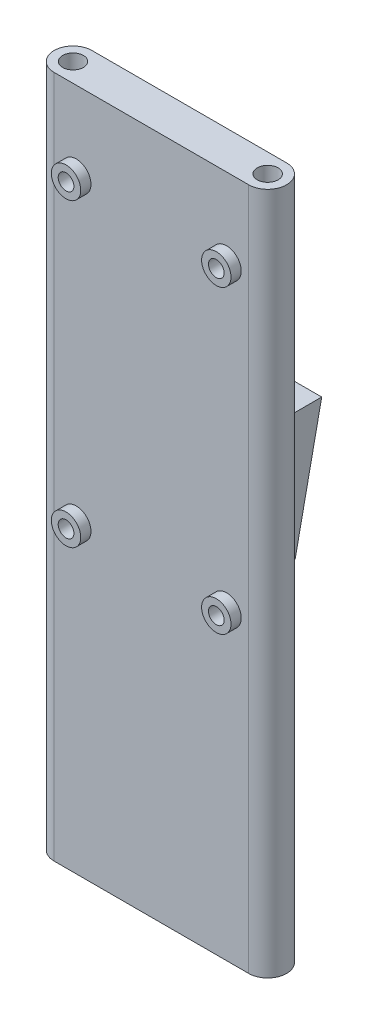
SolidWorks part; units mm, degrees
ref_plane "Front Plane" through (0, 0, 0) normal (0, 0, 1) x (1, 0, 0)
ref_plane "Top Plane" through (0, 0, 0) normal (0, 1, 0) x (1, 0, 0)
ref_plane "Right Plane" through (0, 0, 0) normal (1, 0, 0) x (0, 0, -1)
sketch "Sketch1" plane through (0, 0, 0) normal (0, 1, 0) x (1, 0, 0)
  line L0 (-28.5, 0) -> (28.5, 0) construction
  line L1 (-28.5, 0) -> (28.5, 0) construction
  line L2 (-28.5, 5.55) -> (28.5, 5.55)
  line L3 (-28.5, -5.55) -> (28.5, -5.55)
  circle A0 centre (-28.5, 0) radius 3.05
  circle A1 centre (28.5, 0) radius 3.05
  arc A2 (-28.5, 5.55) -> (-28.5, -5.55) centre (-28.5, 0) ccw
  arc A3 (28.5, -5.55) -> (28.5, 5.55) centre (28.5, 0) ccw
  point P4 (0, 0)
  dimension "D1" = 6.1
  dimension "D2" = 2.5
  dimension "D3" = 57
extrude "Boss-Extrude1" add sketch "Sketch1" along normal mid plane 200
sketch "Sketch2" plane through (0, 0, 0) normal (1, 0, 0) x (0, 0, -1)
  line L0 (5.55, 35.5) -> (5.55, -1.697)
  line L1 (5.55, 100) -> (5.55, -100) construction
  line L2 (5.55, -1.697) -> (8.0456, -1.697)
  line L3 (8.0456, -1.697) -> (15.8164, 35.5)
  line L4 (15.8164, 35.5) -> (5.55, 35.5)
  line L5 (15.0902, 24.6886) -> (8.9553, -4.6774) construction
  line L6 (5.55, 100) -> (-5.55, 100) construction
  dimension "D1" = 64.5
  dimension "D2" = 38
  dimension "D3" = 10.2664
extrude "Boss-Extrude2" add sketch "Sketch2" along normal up to vertex (28.5 mm away) and the other way up to vertex (28.5 mm away) up to point (28.5, 100, -5.55) other way up to point (-28.5, 100, -5.55)
sketch "Sketch3" plane through (0, -1.6815, -8.0488) normal (0, -0.2045, -0.9789) x (-1, 0, 0)
  line L0 (-14, 26.2528) -> (-13.6075, 23.7838) construction
  line L4 (13.7016, -4.2294) -> (14, -1.7472) construction
  circle A0 centre (-14, 26.2528) radius 1.5
  circle A1 centre (-14, -1.7472) radius 1.5
  circle A2 centre (14, 26.2528) radius 1.5
  circle A3 centre (14, -1.7472) radius 1.5
  circle A4 centre (-14, 26.2528) radius 2.5
  circle A5 centre (14, 26.2528) radius 2.5
  circle A6 centre (14, -1.7472) radius 2.5
  circle A7 centre (-14, -1.7472) radius 2.5
  arc A8 (-15.2495, 26.2186) -> (-13.9658, 27.5023) centre (-14, 26.2528) ccw construction
  arc A9 (-15.2495, 26.2186) -> (-13.9658, 27.5023) centre (-14, 26.2528) ccw construction
  dimension "D1" = 3
  dimension "D2" = 28
  dimension "D3" = 28
  dimension "D4" = 1
extrude "Boss-Extrude3" add sketch "Sketch3" along normal blind 1.5
chamfer "Chamfer1" distance 0.5 angle 45 4 edges at (14, -1.2514, -9.6711) (-14, -1.2514, -9.6711) (-14, 26.1569, -15.397) (14, 26.1569, -15.397)
sketch "Sketch4" plane through (0, 0, 5.55) normal (0, 0, 1) x (1, 0, 0)
  line L0 (0, -13.4015) -> (0, 13.4015) construction
  line L1 (-26, 100) -> (26, 100) construction
  line L2 (-26, 100) -> (-26, -15) construction
  line L3 (-26, -15) -> (26, -15) construction
  line L4 (26, 100) -> (26, -15) construction
  line L5 (-28.5, 100) -> (28.5, 100) construction
  line L6 (-22, 77) -> (22, 77) construction
  line L7 (-22, -11) -> (22, -11) construction
  circle A0 centre (-22, 77) radius 2.3
  circle A1 centre (22, 77) radius 2.3
  circle A2 centre (-22, -11) radius 2.3
  circle A3 centre (22, -11) radius 2.3
  circle A4 centre (-22, 77) radius 4.3
  circle A5 centre (22, 77) radius 4.3
  circle A6 centre (-22, -11) radius 4.3
  circle A7 centre (22, -11) radius 4.3
  point P4 (0, 100)
  point P12 (0, 77)
  point P16 (0, -11)
  dimension "D7" = 4.6
  dimension "D1" = 52
  dimension "D2" = 115
  dimension "D3" = 23
  dimension "D4" = 4
  dimension "D5" = 4
  dimension "D6" = 4
  dimension "D8" = 2
extrude "Boss-Extrude4" add sketch "Sketch4" along normal blind 3
extrude "Cut-Extrude1" cut sketch "Sketch4<2>" against normal blind 3 contours A1 | A0 | A3 | A2 region at (-22, 77, 5.55) region at (22, 77, 5.55) region at (-22, -11, 5.55) region at (22, -11, 5.55)
sketch "Sketch4<2>" plane through (0, 0, 5.55) normal (0, 0, 1) x (1, 0, 0) same geometry as "Sketch4"
sketch "Sketch10" plane through (0, 0, -5.55) normal (0, 0, -1) x (-1, 0, 0)
  line L0 (0, 13.4015) -> (0, -13.4015) construction
  line L1 (-24.5, -6.697) -> (24.5, -6.697) construction
  line L2 (-24.5, -6.697) -> (-24.5, -64.697) construction
  line L3 (-24.5, -64.697) -> (24.5, -64.697) construction
  line L4 (24.5, -6.697) -> (24.5, -64.697) construction
  line L5 (-28.5, -1.697) -> (28.5, -1.697) construction
  line L7 (-22.9123, -3.947) -> (-26.0877, -3.947)
  line L8 (-26.0877, -3.947) -> (-27.6754, -6.697)
  line L9 (-27.6754, -6.697) -> (-26.0877, -9.447)
  line L10 (-26.0877, -9.447) -> (-22.9123, -9.447)
  line L11 (-22.9123, -9.447) -> (-21.3246, -6.697)
  line L12 (-21.3246, -6.697) -> (-22.9123, -3.947)
  line L13 (26.0877, -3.947) -> (22.9123, -3.947)
  line L14 (22.9123, -3.947) -> (21.3246, -6.697)
  line L15 (21.3246, -6.697) -> (22.9123, -9.447)
  line L16 (22.9123, -9.447) -> (26.0877, -9.447)
  line L17 (26.0877, -9.447) -> (27.6754, -6.697)
  line L18 (27.6754, -6.697) -> (26.0877, -3.947)
  line L19 (-22.9123, -61.947) -> (-26.0877, -61.947)
  line L20 (-26.0877, -61.947) -> (-27.6754, -64.697)
  line L21 (-27.6754, -64.697) -> (-26.0877, -67.447)
  line L22 (-26.0877, -67.447) -> (-22.9123, -67.447)
  line L23 (-22.9123, -67.447) -> (-21.3246, -64.697)
  line L24 (-21.3246, -64.697) -> (-22.9123, -61.947)
  line L25 (22.9123, -61.947) -> (21.3246, -64.697)
  line L26 (21.3246, -64.697) -> (22.9123, -67.447)
  line L27 (22.9123, -67.447) -> (26.0877, -67.447)
  line L28 (26.0877, -67.447) -> (27.6754, -64.697)
  line L29 (27.6754, -64.697) -> (26.0877, -61.947)
  line L30 (26.0877, -61.947) -> (22.9123, -61.947)
  circle A0 centre (-24.5, -6.697) radius 1.5
  circle A1 centre (24.5, -6.697) radius 1.5
  circle A2 centre (24.5, -64.697) radius 1.5
  circle A3 centre (-24.5, -64.697) radius 1.5
  circle A4 centre (-24.5, -6.697) radius 2.75 construction
  circle A5 centre (24.5, -6.697) radius 2.75 construction
  circle A6 centre (-24.5, -64.697) radius 2.75 construction
  circle A7 centre (24.5, -64.697) radius 2.75 construction
  point P8 (0, -6.697)
  dimension "D1" = 3
  dimension "D2" = 49
  dimension "D3" = 58
  dimension "D4" = 5
  dimension "D5" = 5.5
extrude "Cut-Extrude3" cut sketch "Sketch10" against normal blind 2
extrude "Cut-Extrude4" cut sketch "Sketch10<3>" against normal blind 8 contours A0 | A1 | A3 | A2 region at (24.5, -6.697, -5.55) region at (-24.5, -6.697, -5.55) region at (-24.5, -64.697, -5.55) region at (24.5, -64.697, -5.55)
sketch "Sketch10<3>" plane through (0, 0, -5.55) normal (0, 0, -1) x (-1, 0, 0) same geometry as "Sketch10"
